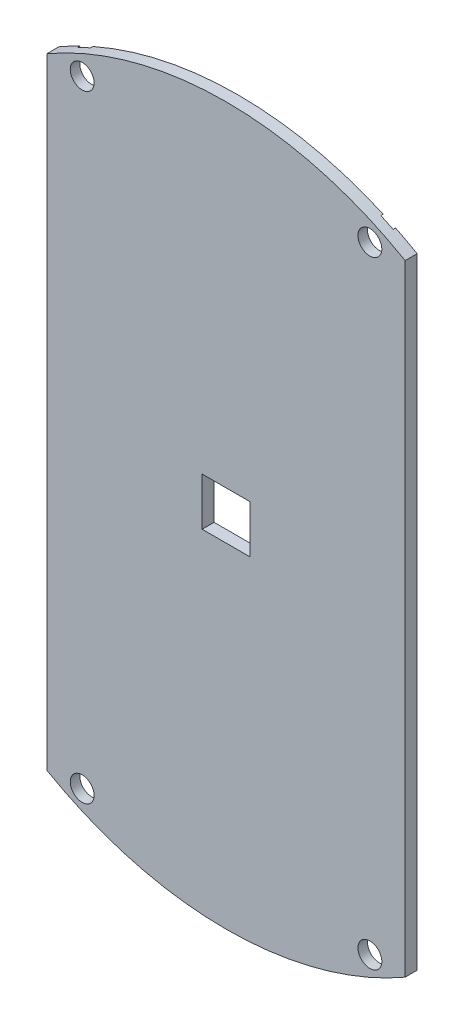
SolidWorks part; units mm, degrees
ref_plane "Front Plane" through (0, 0, 0) normal (0, 0, 1) x (1, 0, 0)
ref_plane "Top Plane" through (0, 0, 0) normal (0, 1, 0) x (1, 0, 0)
ref_plane "Right Plane" through (0, 0, 0) normal (1, 0, 0) x (0, 0, -1)
sketch "Sketch2" plane through (0, 0, 0) normal (0, 0, 1) x (1, 0, 0)
  line L0 (0, 0) -> (-38.1, 0) construction
  line L1 (0, 0) -> (38.1, 0) construction
  line L2 (-38.1, -65.9911) -> (-38.1, 65.9911)
  line L3 (0, 0) -> (0, 68.58) construction
  line L4 (38.1, -65.9911) -> (38.1, 65.9911)
  line L5 (0, 0) -> (0, -72.39) construction
  line L6 (0, 0) -> (0, 5.08) construction
  line L7 (0, 5.08) -> (-5.08, 5.08) construction
  line L8 (-5.08, 5.08) -> (-5.08, -5.08) construction
  line L9 (-5.08, -5.08) -> (5.08, -5.08) construction
  line L10 (5.08, -5.08) -> (5.08, 5.08) construction
  line L11 (5.08, 5.08) -> (0, 5.08) construction
  line L12 (5.08, 5.08) -> (-5.08, 5.08)
  line L13 (-5.08, 5.08) -> (-5.08, -5.08)
  line L14 (-5.08, -5.08) -> (5.08, -5.08)
  line L15 (5.08, -5.08) -> (5.08, 5.08)
  arc A0 (-38.1, -65.9911) -> (38.1, -65.9911) centre (0, 0) ccw
  arc A3 (38.1, 65.9911) -> (-38.1, 65.9911) centre (0, 0) ccw
  circle A4 centre (30.5933, 65.6076) radius 2.54
  circle A5 centre (-30.5933, -65.6076) radius 2.54
  circle A6 centre (-30.5933, 65.6076) radius 2.54
  circle A7 centre (30.5933, -65.6076) radius 2.54
  point P24 (0, 0)
  point P29 (0, 0)
extrude "Boss-Extrude1" add sketch "Sketch2" along normal blind 2.54
sketch "Sketch4" plane through (0, 0, 0) normal (0, 1, 0) x (1, 0, 0)
  line L0 (-38.1, -1.27) -> (38.1, -1.27) construction
  line L1 (-38.1, -2.54) -> (-38.1, 0) construction
  line L2 (38.1, -2.54) -> (38.1, 0) construction
sketch "Sketch5" plane through (0, 0, 0) normal (1, 0, 0) x (0, 0, -1)
  line L0 (-2.54, 0) -> (0, 0) construction
  line L1 (-2.54, -65.9911) -> (-2.54, 65.9911) construction
ref_axis "Axis1" through (0, 0, 2.54) along (0, 0, -1)
sketch "Sketch6" plane through (0, 0, 0) normal (0, 0, 1) x (1, 0, 0)
  arc A0 (30.8827, 69.6613) -> (33.5126, 68.435) centre (30.5933, 65.6076) ccw
  arc A1 (33.5126, 68.435) -> (30.8827, 69.6613) centre (0, 0) ccw
extrude "Cut-Extrude1" cut sketch "Sketch6" along normal blind 0.508
pattern_circular "CirPattern1" count 2 every 50 about axis through (0, 0, 2.54) along (0, 0, -1) of "Cut-Extrude1" reverse direction yes
ref_plane "Plane1" through (0, 0, 0) normal (0, -1, 0) x (-1, 0, 0)
mirror "Mirror2" about plane through (0, 0, 0) normal (0, -1, 0) of "Cut-Extrude1", "CirPattern1"
